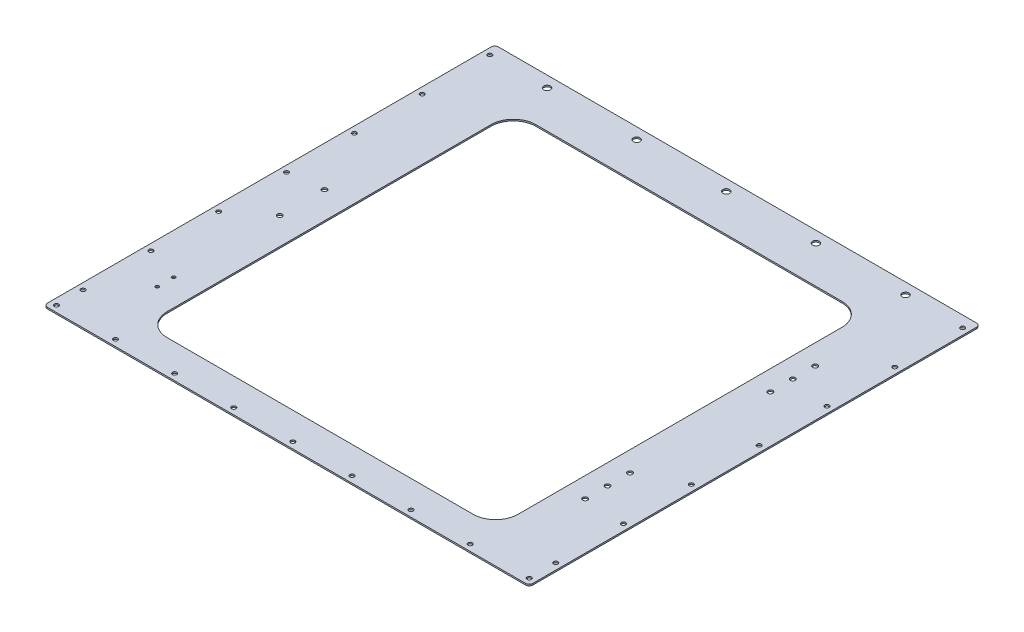
SolidWorks part; units mm, degrees
material "AISI 316 Stainless Steel Sheet (SS)"
ref_plane "Front Plane" through (0, 0, 0) normal (0, 0, 1) x (1, 0, 0)
ref_plane "Top Plane" through (0, 0, 0) normal (0, 1, 0) x (1, 0, 0)
ref_plane "Right Plane" through (0, 0, 0) normal (1, 0, 0) x (0, 0, -1)
sketch "Sketch1" plane through (0, 0, 0) normal (0, 1, 0) x (1, 0, 0)
  line L1 (325, -301.95) -> (-325, -301.95)
  line L2 (325, -301.95) -> (325, 301.95)
  line L3 (325, 301.95) -> (-325, 301.95)
  line L4 (-325, -301.95) -> (-325, 301.95)
  line L5 (325, -301.95) -> (-325, 301.95) construction
  line L6 (325, 301.95) -> (-325, -301.95) construction
  point P0 (0, 0)
  dimension "D1" = 603.9
  dimension "D2" = 650
base flange "Base-Flange1" sketch "Sketch1" thickness 2 reverse thickness direction no parameters "D1"=2
hole_wizard "M8 Clearance Hole1" positions "Sketch6" profile "Sketch7" hole size "M8" standard "ISO" end condition through all
sketch "Sketch6" plane through (0, 0, 0) normal (0, 1, 0) x (1, 0, 0)
  line L0 (0, 0) -> (0, 286.95) construction
  line L3 (240, 286.95) -> (120, 286.95) construction
  line L4 (120, 286.95) -> (0, 286.95) construction
  line L8 (260, 266.95) -> (260, 346.95) construction
  line L9 (-260, 266.95) -> (260, 266.95) construction
  point P2 (240, 286.95)
  point P4 (120, 286.95)
  point P6 (0, 286.95)
  point P30 (-240, 286.95)
  point P31 (-120, 286.95)
  dimension "D1" = 20
  dimension "D2" = 20
sketch "Sketch7" plane through (240, 0, -286.95) normal (1, 0, 0) x (0, 0, 1)
  line L0 (0, 0) -> (0, 2)
  line L1 (0, 2) -> (4.5, 2)
  line L2 (4.5, 2) -> (4.5, 0)
  line L5 (4.5, 0) -> (0, 0)
  line L11 (0, -6.35) -> (0, 107.95) construction
  dimension "Thru Hole Dia." = 9
  dimension "Thru Hole Depth" = 2
sketch "Sketch8" plane through (0, 0, 0) normal (0, 1, 0) x (1, 0, 0)
  line L0 (-325, -301.95) -> (-325, 301.95) construction
  line L1 (205, 236.95) -> (-205, 236.95)
  line L2 (235, 206.95) -> (235, -226.95)
  line L3 (205, -256.95) -> (-205, -256.95)
  line L4 (-235, 206.95) -> (-235, -226.95)
  line L5 (235, 236.95) -> (-235, -256.95) construction
  line L6 (235, -256.95) -> (-235, 236.95) construction
  line L7 (325, 301.95) -> (-325, 301.95) construction
  line L8 (0, -10) -> (0, 0) construction
  line L9 (325, -301.95) -> (-325, -301.95) construction
  arc A0 (205, 236.95) -> (235, 206.95) centre (205, 206.95) cw
  arc A1 (-205, 236.95) -> (-235, 206.95) centre (-205, 206.95) ccw
  arc A2 (-205, -256.95) -> (-235, -226.95) centre (-205, -226.95) cw
  arc A3 (235, -226.95) -> (205, -256.95) centre (205, -226.95) cw
  point P0 (0, -10)
  dimension "D4" = 30
  dimension "D1" = 90
  dimension "D2" = 65
  dimension "D3" = 45
extrude "Cut-Extrude1" cut sketch "Sketch8" against normal blind 10
hole_wizard "M6 Clearance Hole1" positions "Sketch9" profile "Sketch10" hole size "M6" standard "ISO" end condition through all
sketch "Sketch9" plane through (0, 0, 0) normal (0, 1, 0) x (1, 0, 0)
  line L0 (235, -10) -> (358.213, -10) construction
  line L1 (235, -226.95) -> (235, 206.95) construction
  line L3 (262, -104) -> (262, -10) construction
  line L4 (262, -10) -> (262, 84) construction
  line L6 (262, -104) -> (262, -134) construction
  line L7 (262, -134) -> (262, -164) construction
  line L9 (262, 84) -> (262, 114) construction
  line L10 (262, 114) -> (262, 144) construction
  point P0 (262, -164)
  point P2 (262, -134)
  point P4 (262, -104)
  point P6 (262, 84)
  point P8 (262, 114)
  point P10 (262, 144)
  dimension "D1" = 30
  dimension "D2" = 94
  dimension "D3" = 27
sketch "Sketch10" plane through (262, 0, 164) normal (1, 0, 0) x (0, 0, 1)
  line L0 (0, 0) -> (0, 2)
  line L1 (0, 2) -> (3.3, 2)
  line L2 (3.3, 2) -> (3.3, 0)
  line L5 (3.3, 0) -> (0, 0)
  line L11 (0, -6.35) -> (0, 107.95) construction
  dimension "Thru Hole Dia." = 6.6
  dimension "Thru Hole Depth" = 2
hole_wizard "M6 Clearance Hole2" positions "Sketch11" profile "Sketch12" hole size "M6" standard "ISO" end condition through all
sketch "Sketch11" plane through (0, 0, 0) normal (0, 1, 0) x (1, 0, 0)
  line L0 (-271, 20) -> (-271, -40) construction
  line L2 (-271, -10) -> (-235, -10) construction
  line L3 (-235, 206.95) -> (-235, -226.95) construction
  point P0 (-271, 20)
  point P2 (-271, -40)
  dimension "D1" = 36
  dimension "D2" = 60
sketch "Sketch12" plane through (-271, 0, -20) normal (1, 0, 0) x (0, 0, 1)
  line L0 (0, 0) -> (0, 2)
  line L1 (0, 2) -> (3.3, 2)
  line L2 (3.3, 2) -> (3.3, 0)
  line L5 (3.3, 0) -> (0, 0)
  line L11 (0, -6.35) -> (0, 107.95) construction
  dimension "Thru Hole Dia." = 6.6
  dimension "Thru Hole Depth" = 2
hole_wizard "M5 Clearance Hole1" positions "Sketch13" profile "Sketch14" hole size "M5" standard "ISO" end condition through all
sketch "Sketch13" plane through (0, 0, 0) normal (0, 1, 0) x (1, 0, 0)
  line L0 (-316.5, -257.95) -> (-316.5, -293.45) construction
  line L1 (-316.5, -293.45) -> (-316.5, -301.95) construction
  line L2 (-325, -301.95) -> (325, -301.95) construction
  line L4 (-316.5, -293.45) -> (-325, -293.45) construction
  line L5 (-325, 301.95) -> (-325, -301.95) construction
  point P0 (-316.5, 286.95)
  point P3 (-316.5, 196.1333)
  point P6 (-316.5, 105.3167)
  point P9 (-316.5, 14.5)
  point P12 (-316.5, -76.3167)
  point P15 (-316.5, -167.1333)
  point P18 (-316.5, -257.95)
  point P22 (-316.5, -293.45)
sketch "Sketch14" plane through (-316.5, 0, -286.95) normal (1, 0, 0) x (0, 0, 1)
  line L0 (0, 0) -> (0, 2)
  line L1 (0, 2) -> (2.9, 2)
  line L2 (2.9, 2) -> (2.9, 0)
  line L5 (2.9, 0) -> (0, 0)
  line L11 (0, -6.35) -> (0, 107.95) construction
  dimension "Thru Hole Dia." = 5.8
  dimension "Thru Hole Depth" = 2
mirror "Mirror1" about plane through (0, 0, 0) normal (1, 0, 0) of "M5 Clearance Hole1"
hole_wizard "M5 Clearance Hole2" positions "Sketch15" profile "Sketch16" hole size "M5" standard "ISO" end condition through all
sketch "Sketch15" plane through (0, 0, 0) normal (0, 1, 0) x (1, 0, 0)
  line L0 (-316.5, -293.45) -> (-237.375, -293.45) construction
  line L1 (-237.375, -293.45) -> (-158.25, -293.45) construction
  line L2 (-158.25, -293.45) -> (-79.125, -293.45) construction
  line L3 (-79.125, -293.45) -> (0, -293.45) construction
  line L4 (0, -293.45) -> (79.125, -293.45) construction
  line L5 (79.125, -293.45) -> (158.25, -293.45) construction
  line L6 (158.25, -293.45) -> (237.375, -293.45) construction
  line L7 (237.375, -293.45) -> (316.5, -293.45) construction
  point P0 (-237.375, -293.45)
  point P2 (-158.25, -293.45)
  point P4 (-79.125, -293.45)
  point P6 (0, -293.45)
  point P8 (79.125, -293.45)
  point P10 (158.25, -293.45)
  point P12 (237.375, -293.45)
sketch "Sketch16" plane through (-237.375, 0, 293.45) normal (1, 0, 0) x (0, 0, 1)
  line L0 (0, 0) -> (0, 2)
  line L1 (0, 2) -> (2.9, 2)
  line L2 (2.9, 2) -> (2.9, 0)
  line L5 (2.9, 0) -> (0, 0)
  line L11 (0, -6.35) -> (0, 107.95) construction
  dimension "Thru Hole Dia." = 5.8
  dimension "Thru Hole Depth" = 2
hole_wizard "M4 Clearance Hole1" positions "Sketch17" profile "Sketch18" hole size "M4" standard "ISO" end condition through all
sketch "Sketch17" plane through (0, 0, 0) normal (0, 1, 0) x (1, 0, 0)
  point P0 (-270.6, -182.533)
  point P3 (-270.6, -204.533)
sketch "Sketch18" plane through (-270.6, 0, 182.533) normal (1, 0, 0) x (0, 0, 1)
  line L0 (0, 0) -> (0, 2)
  line L1 (0, 2) -> (2.25, 2)
  line L2 (2.25, 2) -> (2.25, 0)
  line L5 (2.25, 0) -> (0, 0)
  line L11 (0, -6.35) -> (0, 107.95) construction
  dimension "Thru Hole Dia." = 4.5
  dimension "Thru Hole Depth" = 2
fillet "Fillet1" radius 5 4 edges at (-325, -1, 301.95) (325, -1, 301.95) (-325, -1, -301.95) (325, -1, -301.95)
sketch "Bend-Lines1" [suppressed] plane through (0, 0, 0) normal (0, 1, 0) x (1, 0, 0)
sketch "Bounding-Box1" [suppressed] plane through (0, 0, 0) normal (0, 1, 0) x (1, 0, 0)
sheet metal parameters "Sheet-Metal1" thickness 2 parameters "D1"=2
flat pattern "Flat-Pattern1" [suppressed]
sketch "Bend-Lines2" plane through (0, 0, 0) normal (0, 1, 0) x (1, 0, 0)
sketch3d "Bounding-Box2" [suppressed]
  line L0 (-425, -289.45, 0) -> (425, -289.45, 0) construction
  line L1 (-425, 289.45, 0) -> (425, 289.45, 0) construction
  line L2 (-425, -289.45, 0) -> (-425, 289.45, 0) construction
  line L3 (425, -289.45, 0) -> (425, 289.45, 0) construction
sheet metal parameters "Sheet-Metal2" thickness 2 parameters "D1"=2
flat pattern "Flat-Pattern1"
sketch "Bend-Lines2" plane through (0, 0, 0) normal (0, 1, 0) x (1, 0, 0)
sketch3d "Bounding-Box2" [suppressed]
  line L0 (325, -301.95, 0) -> (-325, -301.95, 0) construction
  line L1 (325, 301.95, 0) -> (-325, 301.95, 0) construction
  line L2 (325, -301.95, 0) -> (325, 301.95, 0) construction
  line L3 (-325, -301.95, 0) -> (-325, 301.95, 0) construction
sheet metal parameters "Sheet-Metal3" thickness 2 parameters "D1"=2
flat pattern "Flat-Pattern1"
sketch "Bend-Lines2" plane through (0, 0, 0) normal (0, 1, 0) x (1, 0, 0)
sketch3d "Bounding-Box2" [suppressed]
  line L0 (325, -301.95, 0) -> (-325, -301.95, 0) construction
  line L1 (325, 301.95, 0) -> (-325, 301.95, 0) construction
  line L2 (325, -301.95, 0) -> (325, 301.95, 0) construction
  line L3 (-325, -301.95, 0) -> (-325, 301.95, 0) construction
sheet metal parameters "Sheet-Metal4" thickness 2 parameters "D1"=2
flat pattern "Flat-Pattern1"
sketch "Bend-Lines2" plane through (0, 0, 0) normal (0, 1, 0) x (1, 0, 0)
sketch3d "Bounding-Box2" [suppressed]
  line L0 (325, -301.95, 0) -> (-325, -301.95, 0) construction
  line L1 (325, 301.95, 0) -> (-325, 301.95, 0) construction
  line L2 (325, -301.95, 0) -> (325, 301.95, 0) construction
  line L3 (-325, -301.95, 0) -> (-325, 301.95, 0) construction
sheet metal parameters "Sheet-Metal5" thickness 2 parameters "D1"=2
flat pattern "Flat-Pattern1"
sketch "Bend-Lines2" plane through (0, 0, 0) normal (0, 1, 0) x (1, 0, 0)
sketch3d "Bounding-Box2" [suppressed]
  line L0 (325, -301.95, 0) -> (-325, -301.95, 0) construction
  line L1 (325, 301.95, 0) -> (-325, 301.95, 0) construction
  line L2 (325, -301.95, 0) -> (325, 301.95, 0) construction
  line L3 (-325, -301.95, 0) -> (-325, 301.95, 0) construction
sheet metal parameters "Sheet-Metal6" thickness 2 parameters "D1"=2
flat pattern "Flat-Pattern1"
sketch "Bend-Lines2" plane through (0, 0, 0) normal (0, 1, 0) x (1, 0, 0)
sketch3d "Bounding-Box2" [suppressed]
  line L0 (325, -301.95, 0) -> (-325, -301.95, 0) construction
  line L1 (325, 301.95, 0) -> (-325, 301.95, 0) construction
  line L2 (325, -301.95, 0) -> (325, 301.95, 0) construction
  line L3 (-325, -301.95, 0) -> (-325, 301.95, 0) construction
sheet metal parameters "Sheet-Metal7" thickness 2 parameters "D1"=2
flat pattern "Flat-Pattern1"
sketch "Bend-Lines2" plane through (0, 0, 0) normal (0, 1, 0) x (1, 0, 0)
sketch3d "Bounding-Box2" [suppressed]
  line L0 (325, -301.95, 0) -> (-325, -301.95, 0) construction
  line L1 (325, 301.95, 0) -> (-325, 301.95, 0) construction
  line L2 (325, -301.95, 0) -> (325, 301.95, 0) construction
  line L3 (-325, -301.95, 0) -> (-325, 301.95, 0) construction
sheet metal parameters "Sheet-Metal8" thickness 2 parameters "D1"=2
flat pattern "Flat-Pattern1"
sketch "Bend-Lines2" plane through (0, 0, 0) normal (0, 1, 0) x (1, 0, 0)
sketch3d "Bounding-Box2" [suppressed]
  line L0 (325, -301.95, 0) -> (-325, -301.95, 0) construction
  line L1 (325, 301.95, 0) -> (-325, 301.95, 0) construction
  line L2 (325, -301.95, 0) -> (325, 301.95, 0) construction
  line L3 (-325, -301.95, 0) -> (-325, 301.95, 0) construction
sheet metal parameters "Sheet-Metal9" thickness 2 parameters "D1"=2
flat pattern "Flat-Pattern1"
sketch "Bend-Lines2" plane through (0, 0, 0) normal (0, 1, 0) x (1, 0, 0)
sketch3d "Bounding-Box2" [suppressed]
  line L0 (-325, -301.9499, 0) -> (325, -301.95, 0) construction
  line L1 (-325, 301.95, 0) -> (325, 301.9499, 0) construction
  line L2 (-325, -301.9499, 0) -> (-325, 301.95, 0) construction
  line L3 (325, -301.95, 0) -> (325, 301.9499, 0) construction
